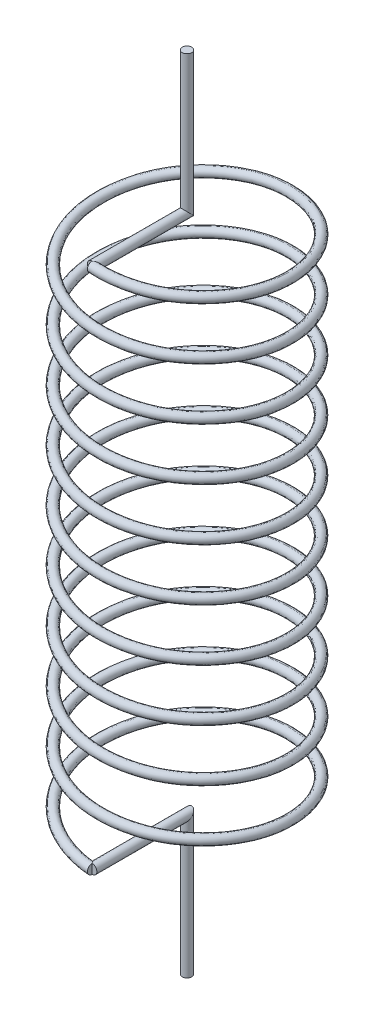
SolidWorks part; units mm, degrees
note: '?' marks a value the reader was unsure of.
ref_plane "Front" through (0, 0, 0) normal (0, 0, 1) x (1, 0, 0)
ref_plane "Top" through (0, 0, 0) normal (0, 1, 0) x (1, 0, 0)
ref_plane "Right" through (0, 0, 0) normal (1, 0, 0) x (0, 0, -1)
sketch "Sketch1" plane through (0, 0, 0) normal (0, 1, 0) x (1, 0, 0)
  circle A0 centre (0, 0) radius 2
ref_axis "Axis1" through (0, 50, 0) along (0, -1, 0)?
curve "Helix/Spiral1" pitch 1.1 height 11 turns 10
sketch "Sketch2" plane through (0, 0, 0) normal (1, 0, 0) x (0, 0, -1)
  circle A0 centre (-2, 0) radius 0.1
  spline S0 degree 3 poles (-2, 0) (-2, 0.0228) (-1.8959, 0.0688) (-1.451, 0.1375) (-0.7853, 0.2063) (0, 0.275) (0.7853, 0.3438) (1.451, 0.4125) (1.8959, 0.4813) (2.0521, 0.55) (1.8959, 0.6188) (1.451, 0.6875) (0.7853, 0.7563) (0, 0.825) (-0.7853, 0.8938) (-1.451, 0.9625) (-1.8959, 1.0313) (-2.0521, 1.1) (-1.8959, 1.1688) (-1.451, 1.2375) (-0.7853, 1.3063) (0, 1.375) (0.7853, 1.4438) (1.451, 1.5125) (1.8959, 1.5813) (2.0521, 1.65) (1.8959, 1.7188) (1.451, 1.7875) (0.7853, 1.8562) (0, 1.925) (-0.7853, 1.9938) (-1.451, 2.0625) (-1.8959, 2.1312) (-2.0521, 2.2) (-1.8959, 2.2687) (-1.451, 2.3375) (-0.7853, 2.4062) (0, 2.475) (0.7853, 2.5437) (1.451, 2.6125) (1.8959, 2.6812) (2.0521, 2.75) (1.8959, 2.8187) (1.451, 2.8875) (0.7853, 2.9562) (0, 3.025) (-0.7853, 3.0937) (-1.451, 3.1625) (-1.8959, 3.2312) (-2.0521, 3.3) (-1.8959, 3.3687) (-1.451, 3.4375) (-0.7853, 3.5062) (0, 3.575) (0.7853, 3.6437) (1.451, 3.7125) (1.8959, 3.7812) (2.0521, 3.85) (1.8959, 3.9187) (1.451, 3.9875) (0.7853, 4.0562) (0, 4.125) (-0.7853, 4.1937) (-1.451, 4.2625) (-1.8959, 4.3312) (-2.0521, 4.4) (-1.8959, 4.4687) (-1.451, 4.5375) (-0.7853, 4.6062) (0, 4.675) (0.7853, 4.7437) (1.451, 4.8125) (1.8959, 4.8812) (2.0521, 4.95) (1.8959, 5.0187) (1.451, 5.0875) (0.7853, 5.1562) (0, 5.225) (-0.7853, 5.2937) (-1.451, 5.3625) (-1.8959, 5.4313) (-2.0521, 5.5) (-1.8959, 5.5688) (-1.451, 5.6375) (-0.7853, 5.7063) (0, 5.775) (0.7853, 5.8438) (1.451, 5.9125) (1.8959, 5.9813) (2.0521, 6.05) (1.8959, 6.1188) (1.451, 6.1875) (0.7853, 6.2563) (0, 6.325) (-0.7853, 6.3938) (-1.451, 6.4625) (-1.8959, 6.5313) (-2.0521, 6.6) (-1.8959, 6.6688) (-1.451, 6.7375) (-0.7853, 6.8063) (0, 6.875) (0.7853, 6.9438) (1.451, 7.0125) (1.8959, 7.0813) (2.0521, 7.15) (1.8959, 7.2188) (1.451, 7.2875) (0.7853, 7.3563) (0, 7.425) (-0.7853, 7.4938) (-1.451, 7.5625) (-1.8959, 7.6313) (-2.0521, 7.7) (-1.8959, 7.7688) (-1.451, 7.8375) (-0.7853, 7.9063) (0, 7.975) (0.7853, 8.0438) (1.451, 8.1125) (1.8959, 8.1813) (2.0521, 8.25) (1.8959, 8.3188) (1.451, 8.3875) (0.7853, 8.4563) (0, 8.525) (-0.7853, 8.5938) (-1.451, 8.6625) (-1.8959, 8.7313) (-2.0521, 8.8) (-1.8959, 8.8688) (-1.451, 8.9375) (-0.7853, 9.0062) (0, 9.075) (0.7853, 9.1437) (1.451, 9.2125) (1.8959, 9.2812) (2.0521, 9.35) (1.8959, 9.4187) (1.451, 9.4875) (0.7853, 9.5562) (0, 9.625) (-0.7853, 9.6937) (-1.451, 9.7625) (-1.8959, 9.8312) (-2.0521, 9.9) (-1.8959, 9.9687) (-1.451, 10.0375) (-0.7853, 10.1062) (0, 10.175) (0.7853, 10.2437) (1.451, 10.3125) (1.8959, 10.3812) (2.0521, 10.45) (1.8959, 10.5187) (1.451, 10.5875) (0.7853, 10.6562) (0, 10.725) (-0.7853, 10.7937) (-1.451, 10.8625) (-1.8959, 10.9312) (-2, 10.9772) (-2, 11) knots 0 0 0 0 0.00625 0.0125 0.01875 0.025 0.03125 0.0375 0.04375 0.05 0.05625 0.0625 0.06875 0.075 0.08125 0.0875 0.09375 0.1 0.10625 0.1125 0.11875 0.125 0.13125 0.1375 0.14375 0.15 0.15625 0.1625 0.16875 0.175 0.18125 0.1875 0.19375 0.2 0.20625 0.2125 0.21875 0.225 0.23125 0.2375 0.24375 0.25 0.25625 0.2625 0.26875 0.275 0.28125 0.2875 0.29375 0.3 0.30625 0.3125 0.31875 0.325 0.33125 0.3375 0.34375 0.35 0.35625 0.3625 0.36875 0.375 0.38125 0.3875 0.39375 0.4 0.40625 0.4125 0.41875 0.425 0.43125 0.4375 0.44375 0.45 0.45625 0.4625 0.46875 0.475 0.48125 0.4875 0.49375 0.5 0.50625 0.5125 0.51875 0.525 0.53125 0.5375 0.54375 0.55 0.55625 0.5625 0.56875 0.575 0.58125 0.5875 0.59375 0.6 0.60625 0.6125 0.61875 0.625 0.63125 0.6375 0.64375 0.65 0.65625 0.6625 0.66875 0.675 0.68125 0.6875 0.69375 0.7 0.70625 0.7125 0.71875 0.725 0.73125 0.7375 0.74375 0.75 0.75625 0.7625 0.76875 0.775 0.78125 0.7875 0.79375 0.8 0.80625 0.8125 0.81875 0.825 0.83125 0.8375 0.84375 0.85 0.85625 0.8625 0.86875 0.875 0.88125 0.8875 0.89375 0.9 0.90625 0.9125 0.91875 0.925 0.93125 0.9375 0.94375 0.95 0.95625 0.9625 0.96875 0.975 0.98125 0.9875 0.99375 1 1 1 1 construction
sweep "Sweep1" add profiles "Sketch2" path "Helix/Spiral1"
sketch "Sketch4" plane through (0, 0, 0) normal (1, 0, 0) x (0, 0, -1)
  line L0 (-2, 0) -> (0, 0)
  line L1 (0, 0) -> (0, -2.9211)
ref_plane "Plane1" through (0, -2.9211, 0) normal (0, 1, 0) x (1, 0, 0)
sketch "Sketch5" plane through (0, -2.9211, 0) normal (0, 1, 0) x (1, 0, 0)
  circle A0 centre (0, 0) radius 0.1
sweep "Sweep2" add profiles "Sketch5" path "Sketch4"
sketch "Sketch6" plane through (0, 0, 0) normal (1, 0, 0) x (0, 0, -1)
  line L0 (-2, 11) -> (0, 11)
  line L1 (0, 11) -> (0, 13.954)
ref_plane "Plane2" through (0, 13.954, 0) normal (0, 1, 0) x (1, 0, 0)
sketch "Sketch7" plane through (0, 13.954, 0) normal (0, 1, 0) x (1, 0, 0)
  circle A0 centre (0, 0) radius 0.1
sweep "Sweep3" add profiles "Sketch7" path "Sketch6"
